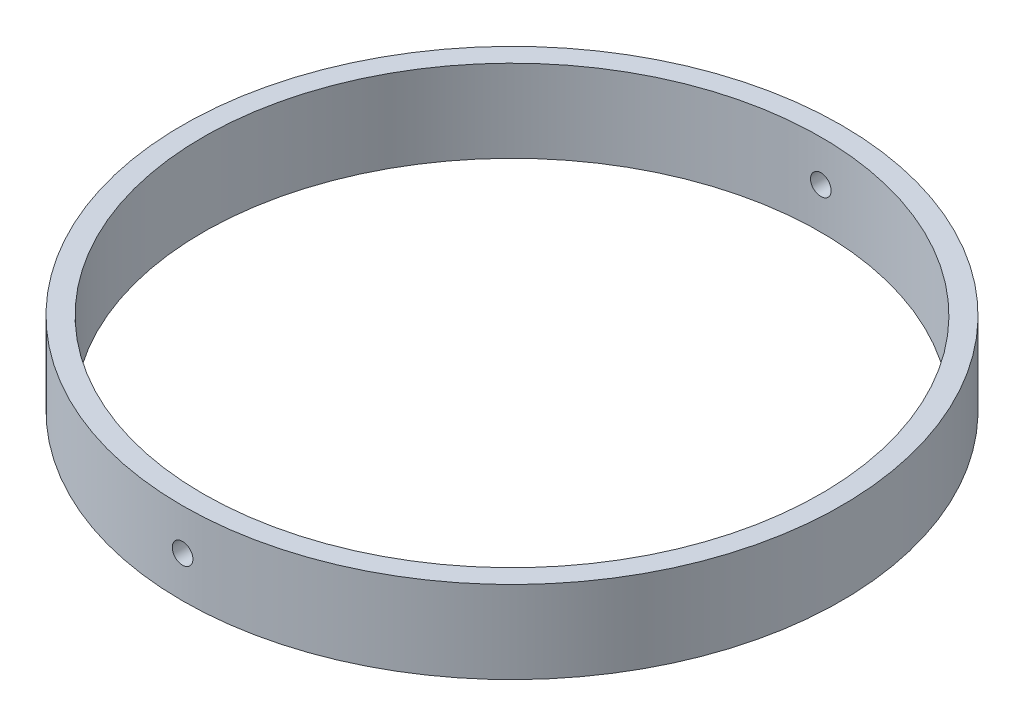
SolidWorks part; units mm, degrees
material "6061-T6 (SS)"
ref_plane "Front Plane" through (0, 0, 0) normal (0, 0, 1) x (1, 0, 0)
ref_plane "Top Plane" through (0, 0, 0) normal (0, 1, 0) x (1, 0, 0)
ref_plane "Right Plane" through (0, 0, 0) normal (1, 0, 0) x (0, 0, -1)
sketch "Sketch1" plane through (0, 0, 0) normal (0, 1, 0) x (1, 0, 0)
  circle A0 centre (0, 0) radius 101.6
  circle A1 centre (0, 0) radius 95.25
  dimension "D1" = 203.2
  dimension "D2" = 190.5
extrude "Boss-Extrude1" add sketch "Sketch1" along normal blind 25.4
sketch "Sketch2" plane through (0, 0, 0) normal (0, 0, 1) x (1, 0, 0)
  circle A0 centre (0, 12.7) radius 3.175
  dimension "D1" = 6.35
extrude "Cut-Extrude1" cut sketch "Sketch2" against normal through all and the other way through all
sketch "Sketch3" plane through (0, 0, 0) normal (1, 0, 0) x (0, 0, -1)
  circle A0 centre (0, 12.7) radius 1.5875
  dimension "D1" = 3.175
extrude "Cut-Extrude3" [suppressed] cut sketch "Sketch3" against normal through all
sketch "Sketch4" plane through (0, 0, 0) normal (1, 0, 0) x (0, 0, -1)
  line L0 (0, 0) -> (0, 72.5565) construction
pattern_circular "CirPattern1" [suppressed] count 24 over 360 about axis through (0, 0, 0) along (0, 1, 0) reverse direction yes of bodies 103
sketch "Sketch5" plane through (0, 25.4, 0) normal (0, 1, 0) x (1, 0, 0)
  circle A0 centre (0, 0) radius 98.425
  circle A1 centre (0, 0) radius 101.6
extrude "Boss-Extrude2" [suppressed] add sketch "Sketch5" along normal blind 146.05
sketch "Sketch6" plane through (0, 0, 0) normal (0, -1, 0) x (1, 0, 0)
  circle A0 centre (0, 0) radius 101.6
  circle A1 centre (0, 0) radius 98.425
extrude "Boss-Extrude3" [suppressed] add sketch "Sketch6" along normal blind 133.35
ref_plane "Plane1" through (0, 0, 101.6) normal (0, 0, 1) x (1, 0, 0)
sketch "Sketch9" plane through (0, 0, 101.6) normal (0, 0, 1) x (1, 0, 0)
  line L0 (-101.6, 0) -> (101.6, 0) construction
  line L1 (0, 0) -> (0, 72.5565) construction
  circle A0 centre (-85.075, 156.8) radius 2.1
  dimension "D1" = 156.8
  dimension "D2" = 85.075
extrude "Cut-Extrude5" [suppressed] cut sketch "Sketch9" against normal through all
